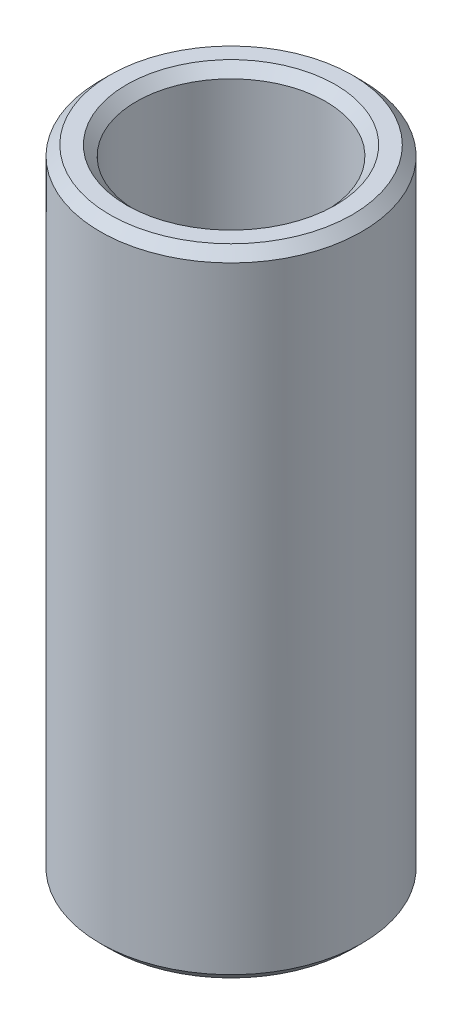
SolidWorks part; units mm, degrees
ref_plane "Front Plane" through (0, 0, 0) normal (0, 0, 1) x (1, 0, 0)
ref_plane "Top Plane" through (0, 0, 0) normal (0, 1, 0) x (1, 0, 0)
ref_plane "Right Plane" through (0, 0, 0) normal (1, 0, 0) x (0, 0, -1)
sketch "Sketch1" plane through (0, 0, 0) normal (0, 1, 0) x (1, 0, 0)
  circle A0 centre (0, 0) radius 42.5
  dimension "SLEEVE_OD" = 85
extrude "Boss-Extrude1" add sketch "Sketch1" along normal blind 206.5178
sketch "Sketch2" plane through (0, 0, 0) normal (0, 1, 0) x (1, 0, 0)
  circle A0 centre (0, 0) radius 30.7565
  dimension "BORE_D" = 61.513
extrude "Cut-Extrude1" cut sketch "Sketch2" along normal through all
chamfer "Chamfer1" distance 3.1631 angle 45 4 edges at (0, 206.5178, 30.7565) (0, 0, 30.7565) (0, 0, 42.5) (0, 206.5178, 42.5)
